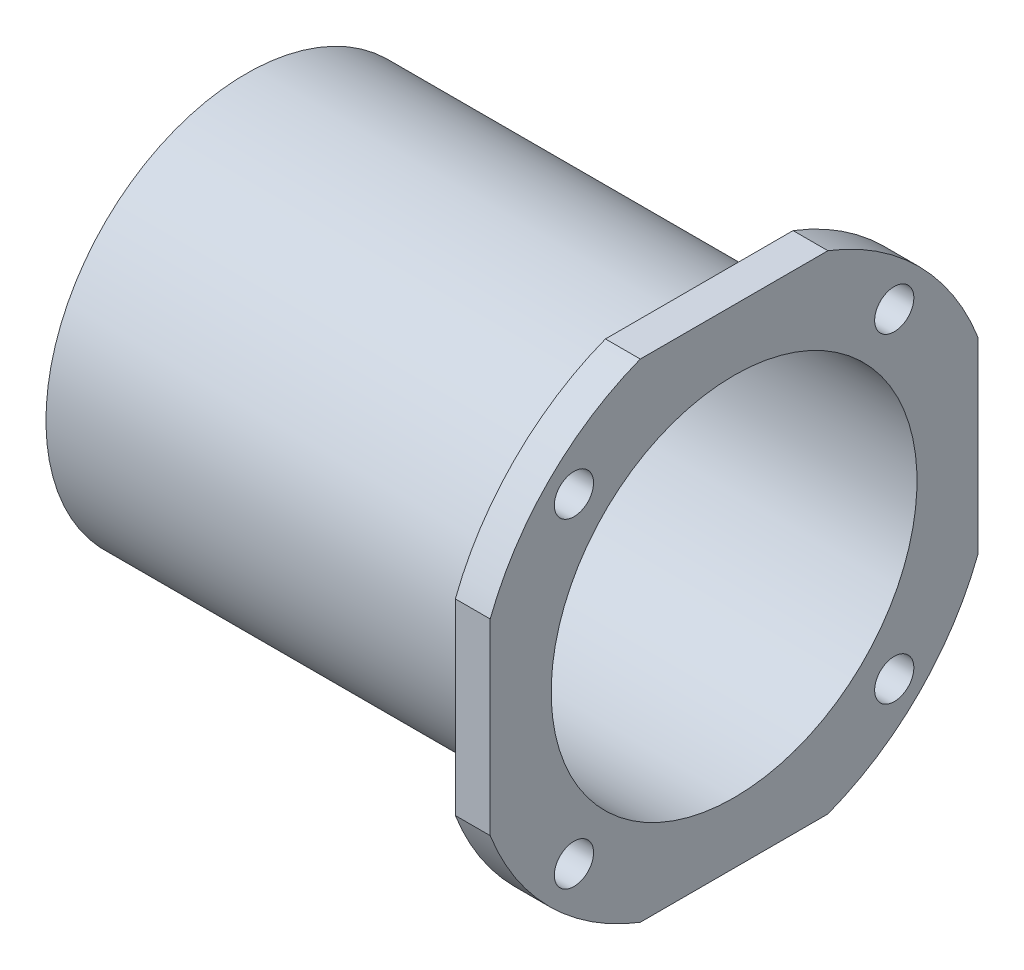
SolidWorks part; units mm, degrees
material "1060 合金"
ref_plane "前视基准面" through (0, 0, 0) normal (0, 0, 1) x (1, 0, 0)
ref_plane "上视基准面" through (0, 0, 0) normal (0, 1, 0) x (1, 0, 0)
ref_plane "右视基准面" through (0, 0, 0) normal (1, 0, 0) x (0, 0, -1)
sketch "草图1" plane through (0, 0, 0) normal (0, 0, 1) x (1, 0, 0)
  line L1 (52, 23) -> (52, 30)
  line L2 (0, 0) -> (20, 0) construction
  line L3 (0, 14) -> (0, 23)
  line L4 (0, 23) -> (52, 23)
  line L5 (56, 21) -> (56, 30)
  line L6 (0, 0) -> (7, 0) construction
  line L7 (52, 30) -> (56, 30)
  line L8 (0, 14) -> (5, 14)
  line L12 (56, 21) -> (5, 21)
  line L13 (5, 14) -> (5, 21)
  dimension "D1" = 21
  dimension "D2" = 14
  dimension "D3" = 2
  dimension "D4" = 4
  dimension "D5" = 5
  dimension "D6" = 52
  dimension "D7" = 7
revolve "旋转2" add sketch "草图1" angle 360 about L2
hole_wizard "打孔尺寸根据十字槽沉头木螺钉的类型2" positions "草图9" profile "草图10" countersink size "M4" standard "GB" end condition through all
sketch "草图9" plane through (0, 0, 0) normal (-1, 0, 0) x (0, 0, 1)
  circle A0 centre (0, 0) radius 17.5 construction
  point P13 (17.5, 0)
  point P14 (0, -17.5)
  point P15 (-17.5, 0)
  point P16 (0, 17.5) [skipped]
  point P17 (0, 17.5)
  dimension "D1" = 35
  dimension "D2" = 4
sketch "草图10" plane through (0, 0, 17.5) normal (0, 1, 0) x (0, 0, 1)
  line L0 (0, 0) -> (0, 56)
  line L1 (0, 56) -> (2.25, 56)
  line L2 (2.25, 56) -> (2.25, 2.55)
  line L3 (2.25, 2.55) -> (4.3, 0.5)
  line L4 (4.3, 0.5) -> (4.3, 0)
  line L6 (4.3, 0) -> (0, 0)
  line L7 (-2.25, 2.55) -> (-4.3, 0.5) construction
  line L11 (0, -6.35) -> (0, 107.95) construction
  dimension "通孔孔直径" = 4.5
  dimension "通孔孔深度" = 56
  dimension "锥形沉头孔直径" = 8.6
  dimension "锥形沉头孔角度" = 90
  dimension "头间隙" = 0.5
sketch "草图18" plane through (56, 0, 0) normal (1, 0, 0) x (0, 0, -1)
  line L1 (-28, -28) -> (28, -28)
  line L2 (-28, -28) -> (-28, 28)
  line L3 (-28, 28) -> (28, 28)
  line L4 (28, -28) -> (28, 28)
  line L5 (-28, -28) -> (28, 28) construction
  line L6 (-28, 28) -> (28, -28) construction
  point P0 (0, 0)
  dimension "D1" = 56
extrude "切除-拉伸3" cut sketch "草图18" against normal up to surface (4 mm away) flip side to cut up to face at (52, -23, 0)
hole_wizard "M4 间隙孔1" positions "草图22" profile "草图21" hole size "M4" standard "GB" end condition up to next
sketch "草图22" plane through (56, 0, 0) normal (1, 0, 0) x (0, 0, -1)
  line L0 (0, 0) -> (18.3848, 18.3848) construction
  line L3 (0, 0) -> (0, 39.9055) construction
  point P0 (18.3848, 18.3848)
  point P31 (18.3848, -18.3848)
  point P32 (-18.3848, -18.3848)
  point P33 (-18.3848, 18.3848)
  dimension "D1" = 26
  dimension "D2" = 45
  dimension "D3" = 4
sketch "草图21" plane through (56, 18.3848, -18.3848) normal (0, 1, 0) x (0, 0, -1)
  line L0 (0, 0) -> (0, 4)
  line L1 (0, 4) -> (2.25, 4)
  line L2 (2.25, 4) -> (2.25, 0)
  line L5 (2.25, 0) -> (0, 0)
  line L11 (0, -6.35) -> (0, 107.95) construction
  dimension "通孔孔直径" = 4.5
  dimension "通孔孔深度" = 4
